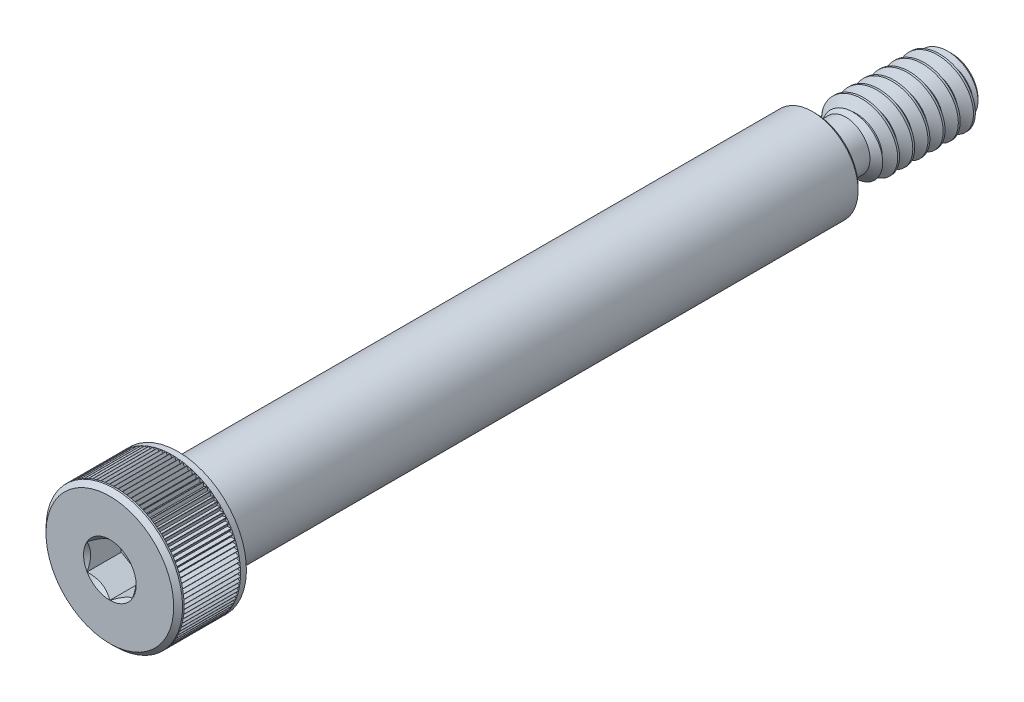
SolidWorks part; units mm, degrees
ref_plane "Front" through (0, 0, 0) normal (0, 0, 1) x (1, 0, 0)
ref_plane "Top" through (0, 0, 0) normal (0, 1, 0) x (1, 0, 0)
ref_plane "Right" through (0, 0, 0) normal (1, 0, 0) x (0, 0, -1)
sketch "Sketch1" plane through (0, 0, 0) normal (1, 0, 0) x (0, 0, -1)
  line L0 (0, 4.7625) -> (4.7625, 4.7625)
  line L1 (4.7625, 4.7625) -> (4.7625, 3.175)
  line L2 (4.7625, 3.175) -> (49.2125, 3.175)
  line L3 (49.2125, 3.175) -> (49.2125, 2.413)
  line L4 (49.2125, 2.413) -> (58.7375, 2.413)
  line L5 (58.7375, 2.413) -> (58.7375, 0)
  line L6 (58.7375, 0) -> (0, 0)
  line L7 (0, 0) -> (0, 4.7625)
  line L8 (0, 4.7625) -> (0, -4.7625) construction
  line L9 (58.7375, 2.413) -> (58.7375, -2.413) construction
  line L10 (49.2125, 3.175) -> (49.2125, -3.175) construction
  line L11 (58.7375, -2.413) -> (57.0597, -2.413) construction
  line L12 (26.9875, 0) -> (26.9875, 3.175) construction
  point P8 (57.15, -2.413)
  point P12 (49.2125, 0)
  point P17 (9.2075, 3.175)
  point P18 (26.9875, 0)
  point P19 (26.9875, 3.175)
  point P20 (44.7675, 3.175)
  point P21 (44.7675, -3.175)
  point P22 (9.2075, -3.175)
  dimension "Head Dia" = 9.525
  dimension "Head Ht" = 4.7625
  dimension "Thread Lg" = 9.525
  dimension "Thread Dia" = 4.826
  dimension "Shoulder Dia" = 6.35
  dimension "Shoulder Lg" = 44.45
  dimension "D1" = 1.5875
  dimension "D2" = 1.6778
  dimension "D3" = 22.225
  dimension "D4" = 4.445
revolve "Revolve1" add sketch "Sketch1" angle 360 mid plane about L6
ref_plane "Plane1" through (0, 0, -58.7375) normal (0, 0, 1) x (1, 0, 0)
sketch "Sketch3" plane through (0, 0, -58.7375) normal (0, 0, 1) x (1, 0, 0)
  circle A0 centre (0, 0) radius 2.413
sketch "Sketch5" plane through (0, 0, 0) normal (1, 0, 0) x (0, 0, -1)
  line L0 (49.2125, 3.175) -> (52.8066, 3.175)
  line L1 (52.8066, 3.175) -> (51.3207, 1.6891)
  line L2 (51.3207, 1.6891) -> (49.9364, 1.6891)
  line L3 (49.2125, 3.175) -> (49.2125, 2.413)
  line L5 (49.2125, 2.413) -> (58.7375, 2.413) construction
  line L6 (58.7375, 0) -> (51.3207, 0) construction
  line L7 (55.0291, 0) -> (55.0291, -2.413) construction
  arc A0 (49.2125, 2.413) -> (49.9364, 1.6891) centre (49.9364, 2.413) ccw
  dimension "D1" = 45
  dimension "CADB" = 2.1082
  dimension "CADA" = 3.3782
revolve "Cut-Revolve1" cut sketch "Sketch5" angle 360 mid plane about L6
chamfer "Chamfer1" distance 0.6032 angle 45 1 edges at (0, 2.413, -58.7375)
chamfer "Chamfer2" distance 0.3096 angle 45 1 edges at (0, 4.7625, 0)
chamfer "Chamfer3" distance 0.2032 angle 45 1 edges at (0, 3.175, -49.2125)
sketch "Sketch10" plane through (0, 0, 0) normal (1, 0, 0) x (0, 0, -1)
  line L0 (0.3096, 0) -> (4.4529, 0) construction
  line L1 (0.3096, -4.7625) -> (0.3096, 4.7625) construction
  line L3 (0.3096, 0) -> (0, 0) construction
  line L4 (4.4529, 0) -> (4.7625, 0) construction
  line L5 (4.7625, -4.7625) -> (4.7625, 4.7625) construction
  point P6 (2.3812, 0)
  dimension "D1" = 4.1434
ref_plane "Plane2" through (0, 0, -2.3812) normal (0, 0, 1) x (1, 0, 0)
sketch "Sketch11" plane through (0, 0, -2.3812) normal (0, 0, 1) x (1, 0, 0)
  line L0 (0, 4.5148) -> (0, 4.7625) construction
  line L1 (0, 4.5148) -> (0.143, 4.7625)
  line L2 (0, 4.5148) -> (-0.143, 4.7625)
  line L3 (-0.143, 4.7625) -> (0.143, 4.7625)
  line L4 (0, 0) -> (-0.143, 4.7625) construction
  line L5 (0.143, 4.7625) -> (0, 0) construction
  circle A1 centre (0, 0) radius 4.7625 construction
  circle A2 centre (0, 0) radius 4.5148 construction
  circle A3 centre (0, 0) radius 4.4529 construction
  point P3 (0, 0.0018)
  point P8 (2.3908, 0.7309)
  dimension "D1" = 0.2476
  dimension "D2" = 3.439
extrude "Cut-Extrude5" cut sketch "Sketch11" against normal mid plane 3.9362
pattern_circular "CirPattern1" count 99 over 360 about axis through (0, 0, -58.7375) along (0, 0, -1) of "Cut-Extrude5"
sketch "Sketch8" plane through (0, 0, 0) normal (0, 0, 1) x (1, 0, 0)
  line L1 (1.5875, 0.9165) -> (0, 1.8331)
  line L2 (0, 1.8331) -> (-1.5875, 0.9165)
  line L3 (-1.5875, 0.9165) -> (-1.5875, -0.9165)
  line L4 (-1.5875, -0.9165) -> (0, -1.8331)
  line L5 (0, -1.8331) -> (1.5875, -0.9165)
  line L6 (1.5875, -0.9165) -> (1.5875, 0.9165)
  circle A0 centre (0, 0) radius 1.5875 construction
  dimension "Hex" = 3.175
extrude "Cut-Extrude2" cut sketch "Sketch8" against normal blind 2.3813
sketch "Sketch9" plane through (0, 0, 0) normal (0, 0, 1) x (1, 0, 0)
  circle A0 centre (0, 0) radius 1.8331
extrude "Cut-Extrude4" cut sketch "Sketch9" against normal blind 2.3813 draft 45
sketch "Front Sketch" plane through (0, 0, 0) normal (0, 0, 1) x (1, 0, 0)
  line L0 (1.5875, -0.9165) -> (1.5875, 0.9165) construction
  line L1 (-1.5875, 0.9165) -> (-1.5875, -0.9165) construction
  circle A0 centre (0, 0) radius 4.7625 construction
  point P4 (-1.5875, 0)
  point P5 (1.5875, 0)
  point P6 (4.7625, 0)
  point P9 (-4.7625, 0)
ref_plane "Contact Plane 1" through (0, 0, -4.7625) normal (0, 0, -1) x (-1, 0, 0)
ref_axis "Center Axis 1" through (0, 0, -58.7375) along (0, 0, 1)
curve "Helix/Spiral1" pitch 1.0583 height 10.5833 radius 2.413 centre (0, 0, -58.7375) axis (0, 0, 1) start towards (0, 1, 0)
sketch "Sketch4" plane through (0, 0, 0) normal (1, 0, 0) x (0, 0, -1)
  line L0 (58.6714, 2.5276) -> (59.7297, 2.5276) construction
  line L1 (59.7297, 2.5276) -> (59.2005, 1.611) construction
  line L3 (59.2005, 1.611) -> (58.6714, 2.5276) construction
  line L4 (58.7044, 2.4703) -> (59.6966, 2.4703) construction
  line L5 (58.7375, 2.413) -> (59.6635, 2.413) construction
  line L6 (59.1344, 1.7256) -> (59.2667, 1.7256) construction
  line L7 (59.2005, 1.7256) -> (59.2005, 1.611) construction
  line L8 (59.2005, 2.5276) -> (59.2005, 2.413) construction
  line L9 (58.7044, 2.4703) -> (59.6966, 2.4703)
  line L10 (59.6966, 2.4703) -> (59.2667, 1.7256)
  line L11 (59.2667, 1.7256) -> (59.1344, 1.7256)
  line L12 (59.1344, 1.7256) -> (58.7044, 2.4703)
  point P14 (59.2005, 2.4703)
  point P15 (59.2005, 2.5276)
  dimension "D1" = 1.0583
  dimension "D2" = 0.1323
sweep "Cut-Sweep1" cut profiles "Sketch4" path "Helix/Spiral1" align with end faces yes
sketch "Sketch12" plane through (0, 0, 0) normal (1, 0, 0) x (0, 0, -1)
  line L1 (49.2125, 2.9718) -> (49.0093, 3.175)
  line L2 (49.0093, 3.175) -> (4.7625, 3.175)
  line L3 (4.7625, 3.175) -> (4.7625, 0)
  line L4 (4.7625, -4.7625) -> (4.7625, 4.7625) construction
  line L5 (4.7625, 0) -> (49.2125, 0)
  line L6 (49.2125, 2.9718) -> (49.2125, 2.413)
  line L7 (51.3207, 1.6891) -> (49.9364, 1.6891) construction
  line L8 (51.3207, 1.6891) -> (49.9364, 1.6891)
  line L9 (51.3207, 1.6891) -> (51.3207, 0)
  line L10 (51.3207, 0) -> (49.2125, 0)
  arc A0 (49.2125, 2.413) -> (49.9364, 1.6891) centre (49.9364, 2.413) ccw construction
  arc A1 (49.2125, 2.413) -> (49.9364, 1.6891) centre (49.9364, 2.413) ccw
revolve "Revolve2" add sketch "Sketch12" angle 360 about L5
equation "\"D3@Helix/Spiral1\" = \"Thread Lg@Sketch1\" + \"D4@Helix/Spiral1\""
equation "\"D1@Chamfer1\" = \"Thread Dia@Sketch1\" * .125"
equation "\"D1@Cut-Extrude2\"= \"Head Ht@Sketch1\" * .5"
equation "\"D1@Cut-Extrude4\" = \"D1@Cut-Extrude2\""
equation "\"D1@Chamfer2\" = \"Head Dia@Sketch1\" * .0325"
equation "\"D1@Sketch1\"=\"D4@Helix/Spiral1\"*1.5"
equation "\"D1@Sketch11\"=\"D1@Chamfer2\"*.8"
equation "\"D1@Cut-Extrude5\"=\"D1@Sketch10\"*.95"
equation "\"D1@CirPattern1\"=(360/\"D2@Sketch11\")-6"
equation "\"D3@Sketch1\"=\"Shoulder Lg@Sketch1\"/2"
equation "\"D4@Sketch1\"=\"D3@Sketch1\"*.2"
equation "\"D1@Sketch4\"=\"D4@Helix/Spiral1\""
equation "\"D2@Sketch4\"=\"D1@Sketch4\"/8"
